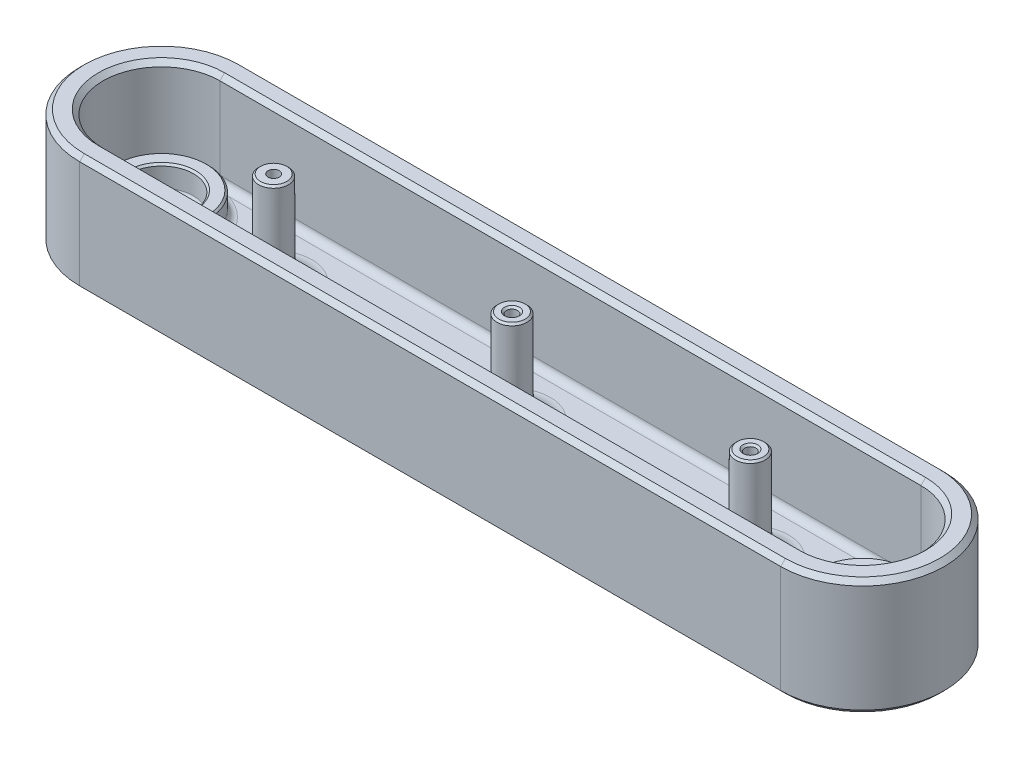
SolidWorks part; units mm, degrees
ref_plane "Front Plane" through (0, 0, 0) normal (0, 0, 1) x (1, 0, 0)
ref_plane "Top Plane" through (0, 0, 0) normal (0, 1, 0) x (1, 0, 0)
ref_plane "Right Plane" through (0, 0, 0) normal (1, 0, 0) x (0, 0, -1)
sketch "Sketch1" plane through (0, 0, 0) normal (0, 1, 0) x (1, 0, 0)
  line L0 (-95.25, 0) -> (95.25, 0) construction
  line L1 (0, -55.9739) -> (0, 55.9739) construction
  line L2 (-95.25, 22.225) -> (95.25, 22.225)
  line L3 (-95.25, -22.225) -> (95.25, -22.225)
  arc A0 (-95.25, 22.225) -> (-95.25, -22.225) centre (-95.25, 0) ccw
  arc A1 (95.25, 22.225) -> (95.25, -22.225) centre (95.25, 0) cw
  point P4 (0, 0)
  point P10 (0, 0)
  dimension "D2" = 44.45
  dimension "D1" = 190.5
extrude "MainBlock" add sketch "Sketch1" along normal blind 31.75
sketch "Sketch2" plane through (0, 31.75, 0) normal (0, 1, 0) x (1, 0, 0)
  line L0 (0, 0) -> (155.7407, 0) construction
  line L1 (0, 0) -> (0, 57.4416) construction
  line L2 (-95.25, -22.225) -> (95.25, -22.225) construction
  line L3 (95.25, 22.225) -> (-95.25, 22.225) construction
  line L4 (-95.25, -22.225) -> (95.25, -22.225) construction
  line L5 (95.25, 22.225) -> (-95.25, 22.225) construction
  line L6 (-95.25, 15.875) -> (95.25, 15.875)
  line L7 (-95.25, -15.875) -> (95.25, -15.875)
  arc A0 (95.25, -22.225) -> (95.25, 22.225) centre (95.25, 0) ccw construction
  arc A1 (-95.25, 22.225) -> (-95.25, -22.225) centre (-95.25, 0) ccw construction
  arc A2 (95.25, -22.225) -> (95.25, 22.225) centre (95.25, 0) ccw construction
  arc A3 (-95.25, 22.225) -> (-95.25, -22.225) centre (-95.25, 0) ccw construction
  arc A4 (-95.25, 15.875) -> (-95.25, -15.875) centre (-95.25, 0) ccw
  arc A5 (95.25, 15.875) -> (95.25, -15.875) centre (95.25, 0) cw
  point P18 (0, 15.875)
  point P19 (0, -15.875)
  dimension "D1" = 6.35
extrude "MainPocket" cut sketch "Sketch2" against normal blind 25.4
sketch "Sketch3" plane through (0, 0, 0) normal (0, -1, 0) x (1, 0, 0)
  line L2 (-95.25, -22.225) -> (95.25, -22.225)
  line L3 (95.25, 22.225) -> (-95.25, 22.225)
  line L4 (-95.25, -22.225) -> (95.25, -22.225) construction
  line L5 (95.25, 22.225) -> (-95.25, 22.225) construction
  circle A0 centre (-95.25, 0) radius 3.81
  circle A1 centre (95.25, 0) radius 3.81
  arc A2 (-95.25, 22.225) -> (-95.25, -22.225) centre (-95.25, 0) ccw
  arc A3 (95.25, -22.225) -> (95.25, 22.225) centre (95.25, 0) ccw
  arc A4 (-95.25, 22.225) -> (-95.25, -22.225) centre (-95.25, 0) ccw construction
  arc A5 (95.25, -22.225) -> (95.25, 22.225) centre (95.25, 0) ccw construction
  dimension "D2" = 7.62
  dimension "D3" = 7.62
extrude "Cut-Extrude1" cut sketch "Sketch3" against normal through all
sketch "Sketch4" plane through (0, 6.35, 0) normal (0, 1, 0) x (1, 0, 0)
  line L0 (0, 0) -> (50000, 0) construction
  line L1 (0, 0) -> (0, 50000) construction
  line L2 (95.25, 15.875) -> (-95.25, 15.875)
  line L3 (-95.25, -15.875) -> (95.25, -15.875)
  line L4 (95.25, 15.875) -> (-95.25, 15.875) construction
  line L5 (-95.25, -15.875) -> (95.25, -15.875) construction
  circle A0 centre (-95.25, 0) radius 8.7313
  circle A1 centre (-95.25, 0) radius 12.7
  arc A2 (95.25, -15.875) -> (95.25, 15.875) centre (95.25, 0) ccw
  arc A3 (-95.25, 15.875) -> (-95.25, -15.875) centre (-95.25, 0) ccw
  arc A4 (95.25, -15.875) -> (95.25, 15.875) centre (95.25, 0) ccw construction
  arc A5 (-95.25, 15.875) -> (-95.25, -15.875) centre (-95.25, 0) ccw construction
  circle A6 centre (95.25, 0) radius 12.7
  circle A7 centre (95.25, 0) radius 8.7313
  dimension "D2" = 17.4625
  dimension "D3" = 25.4
  dimension "D1" = 0
extrude "Boss-Extrude1" add sketch "Sketch4" along normal blind 6.35
sketch "Sketch5" plane through (0, 0, 0) normal (0, -1, 0) x (1, 0, 0)
  line L0 (0, 0) -> (0, 50000) construction
  line L2 (-95.25, -22.225) -> (95.25, -22.225)
  line L3 (95.25, 22.225) -> (-95.25, 22.225)
  line L4 (-95.25, -22.225) -> (95.25, -22.225) construction
  line L5 (95.25, 22.225) -> (-95.25, 22.225) construction
  circle A0 centre (-95.25, 0) radius 6.35
  circle A1 centre (-95.25, 0) radius 3.81 construction
  arc A2 (-95.25, 22.225) -> (-95.25, -22.225) centre (-95.25, 0) ccw
  arc A3 (95.25, -22.225) -> (95.25, 22.225) centre (95.25, 0) ccw
  arc A4 (-95.25, 22.225) -> (-95.25, -22.225) centre (-95.25, 0) ccw construction
  arc A5 (95.25, -22.225) -> (95.25, 22.225) centre (95.25, 0) ccw construction
  circle A6 centre (-95.25, 0) radius 3.81
  circle A7 centre (95.25, 0) radius 3.81 construction
  circle A8 centre (95.25, 0) radius 6.35 construction
  dimension "D2" = 12.7
  dimension "D1" = 0
extrude "Boss-Extrude2" [suppressed] add sketch "Sketch5" along normal blind 3.81
fillet "Fillet1" [suppressed] radius 1.27
sketch "Sketch7" plane through (0, 6.35, 0) normal (0, 1, 0) x (1, 0, 0)
  line L0 (1.3556, 0) -> (50001.3556, 0) construction
  circle A0 centre (0, 0) radius 1.524
  circle A1 centre (-64.77, 0) radius 1.524
  circle A2 centre (-95.25, 0) radius 3.81 construction
  circle A3 centre (95.25, 0) radius 3.81 construction
  circle A4 centre (95.25, 0) radius 3.81 construction
  circle A5 centre (-95.25, 0) radius 3.81 construction
  circle A6 centre (64.77, 0) radius 1.524
  circle A7 centre (-64.77, 0) radius 4.064
  circle A8 centre (0, 0) radius 4.064
  circle A9 centre (64.77, 0) radius 4.064
  dimension "D3" = 3.048
  dimension "D4" = 3.048
  dimension "D5" = 3.048
  dimension "D6" = 8.128
  dimension "D7" = 8.128
  dimension "D8" = 8.128
  dimension "D1" = 30.48
  dimension "D2" = 30.48
extrude "Boss-Extrude3" add sketch "Sketch7" along normal up to surface (25.4 mm away) up to face at (0, 31.75, 0)
fillet "Fillet2" radius 0.635 2 edges at (95.25, 6.35, -8.7313) (-95.25, 6.35, 8.7313)
fillet "Fillet3" radius 1.905 6 edges at (111.125, 6.35, 0) (0, 6.35, 15.875) (-111.125, 6.35, 0) (95.25, 6.35, -12.7) (-95.25, 6.35, -12.7) (0, 6.35, -15.875)
fillet "Fillet6" radius 6.35 3 edges at (64.77, 6.35, -4.064) (0, 6.35, -4.064) (-64.77, 6.35, -4.064)
sketch "Sketch9" plane through (0, 0, 0) normal (0, -1, 0) x (1, 0, 0)
  circle A0 centre (95.25, 0) radius 3.81 construction
  circle A1 centre (95.25, 0) radius 3.81
  circle A6 centre (95.25, 0) radius 6.35
  dimension "D2" = 12.7
extrude "Boss-Extrude4" add sketch "Sketch9" along normal blind 6.35
fillet "Fillet7" radius 1.27 1 edges at (95.25, 0, 6.35)
chamfer "Chamfer1" [suppressed] distance 0.508 angle 45
chamfer "Chamfer2" distance 0.508 angle 45 11 edges at (64.77, 31.75, 1.524) (95.25, 6.35, -3.81) (95.25, 12.7, -12.7) (95.25, 12.7, -8.7313) (-95.25, 6.35, -3.81) (-95.25, 12.7, 12.7) (-64.77, 31.75, 4.064) (0, 31.75, 4.064) (0, 31.75, 1.524) (64.77, 31.75, 4.064) (-95.25, 12.7, 8.7313)
chamfer "Chamfer3" distance 1.27 angle 45 8 edges at (0, 31.75, -22.225) (-117.475, 31.75, 0) (117.475, 31.75, 0) (0, 31.75, 22.225) (0, 31.75, -15.875) (-111.125, 31.75, 0) (111.125, 31.75, 0) (0, 31.75, 15.875)
chamfer "Chamfer4" distance 1.27 angle 45 4 edges at (0, 0, -22.225) (-117.475, 0, 0) (117.475, 0, 0) (0, 0, 22.225)
equation "\"D3@Sketch3\"=\"D2@Sketch3\""
equation "\"D5@Sketch7\"=\"D3@Sketch7\""
equation "\"D4@Sketch7\"=\"D3@Sketch7\""
equation "\"D7@Sketch7\"=\"D6@Sketch7\""
equation "\"D8@Sketch7\"=\"D6@Sketch7\""
